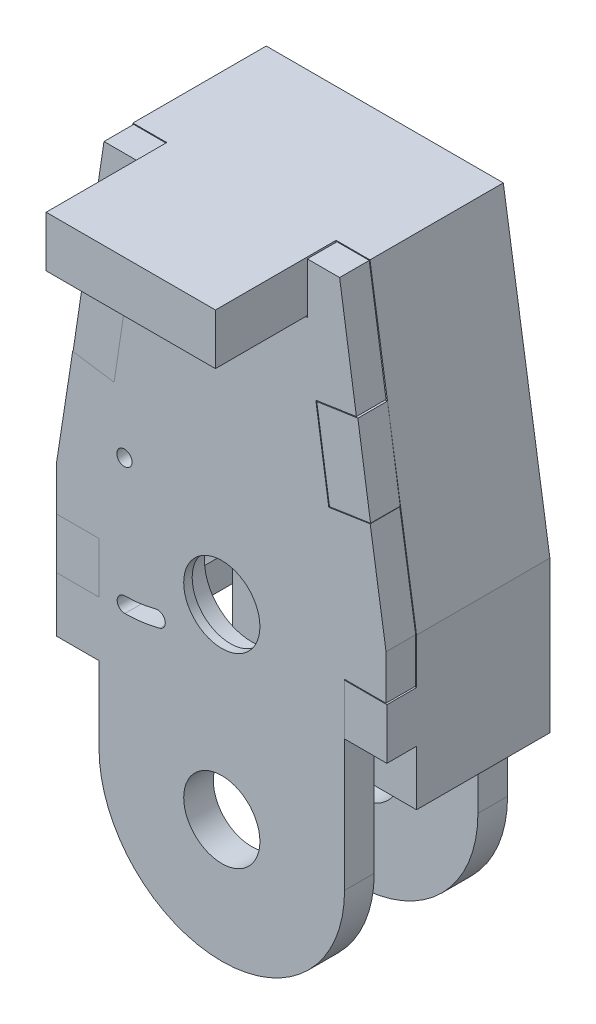
SolidWorks part; units mm, degrees
ref_plane "Front Plane" through (0, 0, 0) normal (0, 0, 1) x (1, 0, 0)
ref_plane "Top Plane" through (0, 0, 0) normal (0, 1, 0) x (1, 0, 0)
ref_plane "Right Plane" through (0, 0, 0) normal (1, 0, 0) x (0, 0, -1)
sketch "Sketch1" plane through (0, 0, 0) normal (0, 0, 1) x (1, 0, 0)
  line L0 (20, -72) -> (-20, -72)
  line L1 (-20, -72) -> (-20, 0)
  line L2 (20, 0) -> (20, -72)
  line L3 (-20, -60) -> (20, -60)
  arc A0 (-20, 0) -> (20, 0) centre (0, 0) cw
  circle A1 centre (0, 0) radius 4
  arc A2 (-16, 12) -> (16, 12) centre (0, -13.3772) cw
  dimension "D1" = 20
  dimension "D3" = 8
  dimension "D5" = 30
  dimension "D2" = 60
  dimension "D4" = 12
  dimension "D6" = 12
extrude "Boss-Extrude1" add sketch "Sketch1" along normal mid plane 60 contours A0 L1 L3 L2 A1 | L3 L1 L0 L2 region at (0, -66, 0) region at (0, -23.4559, 0)
extrude "Cut-Extrude1" cut sketch "Sketch1<3>" against normal mid plane 35 contours A0 L1 L3 L2 A1 region at (0, -23.4559, 0)
sketch "Sketch1<3>" plane through (0, 0, 0) normal (0, 0, 1) x (1, 0, 0) same geometry as "Sketch1"
sketch "Sketch2" plane through (0, 0, -30) normal (0, 0, -1) x (-1, 0, 0)
  line L0 (-29, -132) -> (-29, -167)
  line L10 (-29, -167) -> (-39, -167)
  line L12 (29, -167) -> (39, -167)
  line L17 (0, 0) -> (0, -236.1713) construction
  line L18 (-20, -72) -> (-29, -132)
  line L22 (20, -72) -> (29, -132)
  line L23 (-20, -72) -> (20, -72)
  line L24 (-39, -131.2542) -> (-39, -185)
  line L26 (39, -131.2542) -> (39, -185)
  line L30 (-28.6119, -62) -> (28.6119, -62) construction
  line L32 (39, -131.2542) -> (28, -60)
  line L35 (-39, -185) -> (39, -185) construction
  line L36 (-29, -175) -> (29, -175) construction
  line L37 (29, -132) -> (29, -175) construction
  line L38 (-29, -132) -> (-29, -175) construction
  line L39 (29, -132) -> (29, -167)
  line L40 (-29, -167) -> (-29, -185)
  line L41 (29, -167) -> (29, -185)
  line L42 (-28.6119, -62) -> (-39, -131.2542) construction
  line L43 (28.6119, -62) -> (39, -131.2542) construction
  line L44 (28, -60) -> (20, -60)
  line L45 (-28, -60) -> (-20, -60)
  line L46 (-39, -131.2542) -> (-28, -60)
  circle A0 centre (0, -185) radius 11.1 construction
  arc A2 (39, -185) -> (-39, -185) centre (0, -185) cw construction
  arc A3 (-29, -185) -> (29, -185) centre (0, -185) ccw
  point P10 (0, -185)
  line M11 (-20, 0) -> (-20, -72)
  line M12 (-20, -72) -> (20, -72)
  line M13 (20, -72) -> (20, 0)
  dimension "D6" = 22.2
  dimension "D5" = 35
  dimension "D1" = 58
  dimension "D2" = 60
  dimension "D3" = 10
  dimension "D4" = 8
  dimension "D7" = 185
extrude "Boss-Extrude2" add sketch "Sketch2" against normal blind 7 contours M12 region at (0, -143.5794, -30)
extrude "Boss-Extrude3" add sketch "Sketch2<3>" against normal blind 31.5 contours L22 L39 L12 L26 M13 | L24 L10 L0 L18 M11 region at (30.4885, -114.185, -30) region at (-30.4885, -114.185, -30)
sketch "Sketch2<3>" plane through (0, 0, -30) normal (0, 0, -1) x (-1, 0, 0) same geometry as "Sketch2"
sketch "Sketch4" plane through (0, 0, -23) normal (0, 0, 1) x (1, 0, 0)
  line L0 (20, -72) -> (-20, -72) construction
  line L1 (-21, -114) -> (21, -114)
  line L2 (-21, -114) -> (-21, -72)
  line L3 (-21, -72) -> (21, -72)
  line L4 (21, -114) -> (21, -72)
  line L5 (-21, -114) -> (21, -72) construction
  line L6 (-21, -72) -> (21, -114) construction
  line L7 (-15.5, -108.5) -> (15.5, -108.5) construction
  line L8 (-15.5, -108.5) -> (-15.5, -77.5) construction
  line L9 (-15.5, -77.5) -> (15.5, -77.5) construction
  line L10 (15.5, -108.5) -> (15.5, -77.5) construction
  line L11 (-15.5, -108.5) -> (15.5, -77.5) construction
  line L12 (-15.5, -77.5) -> (15.5, -108.5) construction
  line L13 (15.5, -112) -> (15.5, -105) construction
  line L14 (13.7, -112) -> (13.7, -105)
  line L15 (17.3, -112) -> (17.3, -105)
  line L16 (15.5, -81) -> (15.5, -74) construction
  line L17 (13.7, -81) -> (13.7, -74)
  line L18 (17.3, -81) -> (17.3, -74)
  line L19 (-15.5, -81) -> (-15.5, -74) construction
  line L20 (-17.3, -81) -> (-17.3, -74)
  line L21 (-13.7, -81) -> (-13.7, -74)
  line L22 (-15.5, -112) -> (-15.5, -105) construction
  line L23 (-17.3, -112) -> (-17.3, -105)
  line L24 (-13.7, -112) -> (-13.7, -105)
  line L25 (0, -96.5) -> (0, -89.5) construction
  line L26 (-11.1, -96.5) -> (-11.1, -89.5)
  line L27 (11.1, -96.5) -> (11.1, -89.5)
  arc A0 (13.7, -112) -> (17.3, -112) centre (15.5, -112) ccw
  arc A1 (17.3, -105) -> (13.7, -105) centre (15.5, -105) ccw
  arc A2 (13.7, -81) -> (17.3, -81) centre (15.5, -81) ccw
  arc A3 (17.3, -74) -> (13.7, -74) centre (15.5, -74) ccw
  arc A4 (-17.3, -81) -> (-13.7, -81) centre (-15.5, -81) ccw
  arc A5 (-13.7, -74) -> (-17.3, -74) centre (-15.5, -74) ccw
  arc A6 (-17.3, -112) -> (-13.7, -112) centre (-15.5, -112) ccw
  arc A7 (-13.7, -105) -> (-17.3, -105) centre (-15.5, -105) ccw
  arc A8 (-11.1, -96.5) -> (11.1, -96.5) centre (0, -96.5) ccw
  arc A9 (11.1, -89.5) -> (-11.1, -89.5) centre (0, -89.5) ccw
  point P0 (0, -93)
  point P5 (0, -93)
  point P15 (15.5, -108.5)
  point P21 (15.5, -77.5)
  point P28 (-15.5, -77.5)
  point P35 (-15.5, -108.5)
  point P43 (0, -93)
  dimension "D4" = 1.8
  dimension "D6" = 11.1
  dimension "D1" = 42
  dimension "D2" = 21
  dimension "D3" = 31
  dimension "D5" = 7
  dimension "D7" = 7
extrude "Cut-Extrude2" cut sketch "Sketch4" against normal through all contours L24 A7 L23 A6 | L15 A1 L14 A0 | L18 A3 L17 A2 | L27 A9 L26 A8 | L21 A5 L20 A4 | L24 A7 L23 A6 | L15 A1 L14 A0 | L18 A3 L17 A2 region at (15.5, -108.5, -23) region at (15.5, -77.5, -23) region at (-15.5, -77.5, -23) region at (-15.5, -108.5, -23) region at (0, -93, -23)
sketch "Sketch5" plane through (0, 0, -23) normal (0, 0, 1) x (1, 0, 0)
  circle A0 centre (0, -141) radius 11.1
  circle A1 centre (0, -185) radius 11.1
  circle A2 centre (0, -141) radius 9
  circle A3 centre (0, -185) radius 9
  dimension "D2" = 22.2
  dimension "D4" = 22.2
  dimension "D5" = 18
  dimension "D6" = 18
  dimension "D1" = 48
  dimension "D3" = 44
extrude "Cut-Extrude3" cut sketch "Sketch5" against normal through all contours A3 | A2 region at (0, -141, -23) region at (0, -185, -23)
extrude "Cut-Extrude4" cut sketch "Sketch5<3>" against normal blind 5
sketch "Sketch5<3>" plane through (0, 0, -23) normal (0, 0, 1) x (1, 0, 0) same geometry as "Sketch5"
sketch "Sketch8" plane through (0, 0, 1.5) normal (0, 0, 1) x (1, 0, 0)
  line L0 (0, -54.5477) -> (0, -241.8797) construction
  line L1 (-22.4398, -88.2655) -> (-32.1389, -86.8107)
  line L2 (-20, -72) -> (-29, -132) construction
  line L4 (-32.1389, -86.8107) -> (-35.1389, -106.8107)
  line L5 (-35.1389, -106.8107) -> (-25.4398, -108.2655)
  line L6 (-20, -72) -> (-29, -132) construction
  line L7 (-25.4398, -108.2655) -> (-22.4398, -88.2655)
  line L8 (-39, -131.2542) -> (-39, -167) construction
  line L9 (-39, -142) -> (-29, -142)
  line L10 (-39, -142) -> (-39, -154)
  line L11 (-39, -154) -> (-29, -154)
  line L12 (-29, -142) -> (-29, -154)
  line L13 (-29, -132) -> (-29, -167) construction
  line L14 (29, -142) -> (29, -154)
  line L15 (39, -154) -> (29, -154)
  line L16 (39, -142) -> (39, -154)
  line L17 (39, -142) -> (29, -142)
  line L18 (25.4398, -108.2655) -> (22.4398, -88.2655)
  line L19 (35.1389, -106.8107) -> (25.4398, -108.2655)
  line L20 (32.1389, -86.8107) -> (35.1389, -106.8107)
  line L21 (22.4398, -88.2655) -> (32.1389, -86.8107)
  line L22 (-39, -131.2542) -> (-28, -60) construction
  point P7 (-32.139, -86.8107)
  dimension "D1" = 12
  dimension "D2" = 20
  dimension "D3" = 10
  dimension "D4" = 24
extrude "Boss-Extrude4" add sketch "Sketch8" along normal blind 7
sketch "Sketch11" plane through (0, 0, 1.5) normal (0, 0, 1) x (1, 0, 0)
  line L0 (0, -35.9893) -> (0, -185) construction
  line L1 (-20, -72) -> (-20, -60)
  line L2 (-20, -60) -> (-28, -60)
  line L3 (-28, -60) -> (-32.0242, -86.8279)
  line L4 (-32.0242, -86.8279) -> (-22.4398, -88.2655)
  line L5 (-25.4398, -108.2655) -> (-35.218, -106.756)
  line L6 (-35.218, -106.756) -> (-39, -131.2542)
  line L7 (-39, -131.2542) -> (-39, -142)
  line L8 (-39, -142) -> (-29, -142)
  line L9 (-29, -154) -> (-29, -142) construction
  line L10 (-29, -132) -> (-29, -167) construction
  line L11 (-29, -154) -> (-39, -154)
  line L12 (-39, -154) -> (-39, -167)
  line L13 (-39, -167) -> (-29, -167)
  line L14 (29, -167) -> (29, -185) construction
  line L15 (-29, -167) -> (-29, -185) construction
  line L16 (29, -167) -> (29, -185)
  line L17 (-29, -167) -> (-29, -185)
  line L18 (29, -167) -> (29, -185)
  line L19 (-29, -167) -> (-29, -185)
  line L20 (39, -167) -> (29, -167)
  line L21 (39, -154) -> (39, -167)
  line L22 (29, -154) -> (39, -154)
  line L23 (39, -142) -> (29, -142)
  line L24 (39, -131.2542) -> (39, -142)
  line L25 (35.218, -106.756) -> (39, -131.2542)
  line L26 (25.4398, -108.2655) -> (35.218, -106.756)
  line L27 (32.0242, -86.8279) -> (22.4398, -88.2655)
  line L28 (28, -60) -> (32.0242, -86.8279)
  line L29 (20, -60) -> (28, -60)
  line L30 (20, -72) -> (20, -60)
  line L31 (20, -72) -> (-20, -72)
  line L32 (-22.4398, -88.2655) -> (-25.4398, -108.2655)
  line L33 (-29, -142) -> (-29, -154)
  line L34 (22.4398, -88.2655) -> (25.4398, -108.2655)
  line L35 (29, -132) -> (29, -167)
  line L36 (25.4398, -108.2655) -> (29, -132) construction
  line L37 (20, -72) -> (29, -132) construction
  line L38 (38.8, -141.8) -> (29, -141.8)
  line L39 (38.8, -131.2695) -> (38.8, -141.8)
  line L40 (35.0509, -106.9842) -> (38.8, -131.2695)
  line L41 (25.2718, -108.4938) -> (35.0509, -106.9842)
  line L42 (22.2124, -88.0974) -> (25.2718, -108.4938)
  line L43 (31.7967, -86.6598) -> (22.2124, -88.0974)
  line L44 (27.8278, -60.2) -> (31.7967, -86.6598)
  line L45 (20.2, -60.2) -> (27.8278, -60.2)
  line L46 (20.2, -72.2) -> (20.2, -60.2)
  line L47 (20.2, -72.2) -> (-20.2, -72.2)
  line L48 (-20.2, -72.2) -> (-20.2, -60.2)
  line L49 (-20.2, -60.2) -> (-27.8278, -60.2)
  line L50 (-27.8278, -60.2) -> (-31.7967, -86.6598)
  line L51 (-31.7967, -86.6598) -> (-22.2124, -88.0974)
  line L52 (-22.2124, -88.0974) -> (-25.2718, -108.4938)
  line L53 (-25.2718, -108.4938) -> (-35.0509, -106.9842)
  line L54 (-35.0509, -106.9842) -> (-38.8, -131.2695)
  line L55 (-38.8, -131.2695) -> (-38.8, -141.8)
  line L56 (-38.8, -141.8) -> (-28.8, -141.8)
  line L57 (-28.8, -141.8) -> (-28.8, -154.2)
  line L58 (-28.8, -154.2) -> (-38.8, -154.2)
  line L59 (-38.8, -154.2) -> (-38.8, -166.8)
  line L60 (-38.8, -166.8) -> (-28.8, -166.8)
  line L61 (-28.8, -166.8) -> (-28.8, -185)
  line L62 (28.8, -167) -> (28.8, -185)
  line L63 (29.2, -167) -> (29.2, -185)
  line L64 (-28.8, -167) -> (-28.8, -185)
  line L65 (29, -153.8) -> (39.2, -153.8)
  line L66 (39.2, -153.8) -> (39.2, -167.2)
  line L67 (39.2, -167.2) -> (29, -167.2)
  line L68 (29.2, -132) -> (29.2, -167)
  line L69 (-32.1389, -86.8107) -> (-28, -60) construction
  line L70 (-28, -60) -> (-20, -60) construction
  line L71 (-39, -131.2542) -> (-32.1389, -86.8107) construction
  arc A0 (-29, -185) -> (29, -185) centre (0, -185) ccw construction
  arc A1 (-29, -185) -> (29, -185) centre (0, -185) ccw
  arc A2 (-28.8, -185) -> (28.8, -185) centre (0, -185) ccw
  point P9 (-35.1389, -106.8107)
  point P11 (-34.7068, -106.6486)
  point P16 (-39, -135.7638)
  point P34 (-28, -60)
  point P101 (0, 0)
  point P102 (-35.2181, -106.7565)
  line M2 (-22.4398, -88.2655) -> (-20, -72)
  dimension "D1" = 0.2
extrude "Boss-Extrude6" add sketch "Sketch11" along normal blind 7 separate body contours L17 A1 L18 L16 L35 L38 L39 L40 L41 L42 L43 L44 L45 L46 L47 | L50 L51 L47 L48 L49 M2 region at (-25.3094, -74.265, 1.5) region at (0.1626, -140.3513, 1.5)
sketch "Sketch12" plane through (0, 0, 1.5) normal (0, 0, -1) x (-1, 0, 0)
  circle A1 centre (0, -185) radius 9
  circle A2 centre (0, -185) radius 9
  circle A3 centre (0, -141) radius 9
  circle A4 centre (0, -141) radius 9
  circle A5 centre (0, -185) radius 11.1
  circle A6 centre (0, -185) radius 11.1
  circle A7 centre (0, -141) radius 11.1
  circle A8 centre (0, -141) radius 11.1
  dimension "D1" = 0
  dimension "D2" = 0
  dimension "D3" = 0
  dimension "D4" = 0
extrude "Cut-Extrude5" cut sketch "Sketch12" against normal through all contours A4 | A2
extrude "Cut-Extrude8" cut sketch "Sketch12<6>" against normal blind 5 contours A8 A4 region at (10.786, -141, 1.5)
sketch "Sketch12<6>" plane through (0, 0, 1.5) normal (0, 0, -1) x (-1, 0, 0) same geometry as "Sketch12"
sketch "Sketch14" plane through (0, 0, 8.5) normal (0, 0, 1) x (1, 0, 0)
  line L0 (-23, -122.5) -> (-22.915, -152.4999) construction
  line L1 (-23, -122.5) -> (-15.1534, -151.4557) construction
  line L2 (-23, -122.5) -> (-19, -152.2321) construction
  line L4 (-39, -154) -> (-39, -167) construction
  circle A0 centre (0, -141) radius 8.15 construction
  circle A1 centre (0, -185) radius 25.65 construction
  circle A2 centre (-23, -122.5) radius 1.8
  arc A3 (-22.915, -152.4999) -> (-15.1534, -151.4557) centre (-23, -122.5) ccw construction
  arc A4 (-22.9099, -154.2999) -> (-14.6826, -153.193) centre (-23, -122.5) ccw
  arc A5 (-22.9201, -150.6999) -> (-15.6242, -149.7183) centre (-23, -122.5) ccw
  arc A6 (-22.9201, -150.6999) -> (-22.9099, -154.2999) centre (-22.915, -152.4999) ccw
  arc A7 (-14.6826, -153.193) -> (-15.6242, -149.7183) centre (-15.1534, -151.4557) ccw
  point P12 (-19, -152.2321)
  dimension "D1" = 51.3
  dimension "D2" = 16.3
  dimension "D3" = 3.6
  dimension "D4" = 1.8
  dimension "D6" = 30
  dimension "D5" = 15
  dimension "D7" = 18.5
  dimension "D8" = 23
  dimension "D9" = 20
extrude "Cut-Extrude9" cut sketch "Sketch14" against normal up to surface (7 mm away) contours A4 A7 A5 A6 | A2 | A2 | A5 A6 A4 A7 region at (-23, -122.5, 8.5) region at (-19.0175, -152.1024, 8.5) up to face at (-11.1, -141, 1.5)
sketch "Sketch15" plane through (0, 0, -23) normal (0, 0, 1) x (1, 0, 0)
  line L1 (-29, -154) -> (-29, -167) construction
  line L2 (-29, -132) -> (-29, -167) construction
  line L4 (-29, -145) -> (-29, -160)
  arc A0 (-29, -145) -> (-29, -160) centre (-20.9533, -152.5) ccw
  dimension "D1" = 11
  dimension "D2" = 15
  dimension "D3" = 22.5
extrude "Cut-Extrude10" cut sketch "Sketch15" along normal up to surface (24.5 mm away) up to face at (-34, -160.5, 1.5)
sketch "Sketch16" plane through (0, -60, 0) normal (0, 1, 0) x (1, 0, 0)
  line L1 (-40, -37.5) -> (40, -37.5)
  line L2 (-40, -37.5) -> (-40, 37.5)
  line L3 (-40, 37.5) -> (40, 37.5)
  line L4 (40, -37.5) -> (40, 37.5)
  line L5 (-40, -37.5) -> (40, 37.5) construction
  line L6 (-40, 37.5) -> (40, -37.5) construction
  point P0 (0, 0)
  point P5 (0, 0)
  dimension "D1" = 75
  dimension "D2" = 80
extrude "Cut-Extrude11" cut sketch "Sketch16" along normal through all
